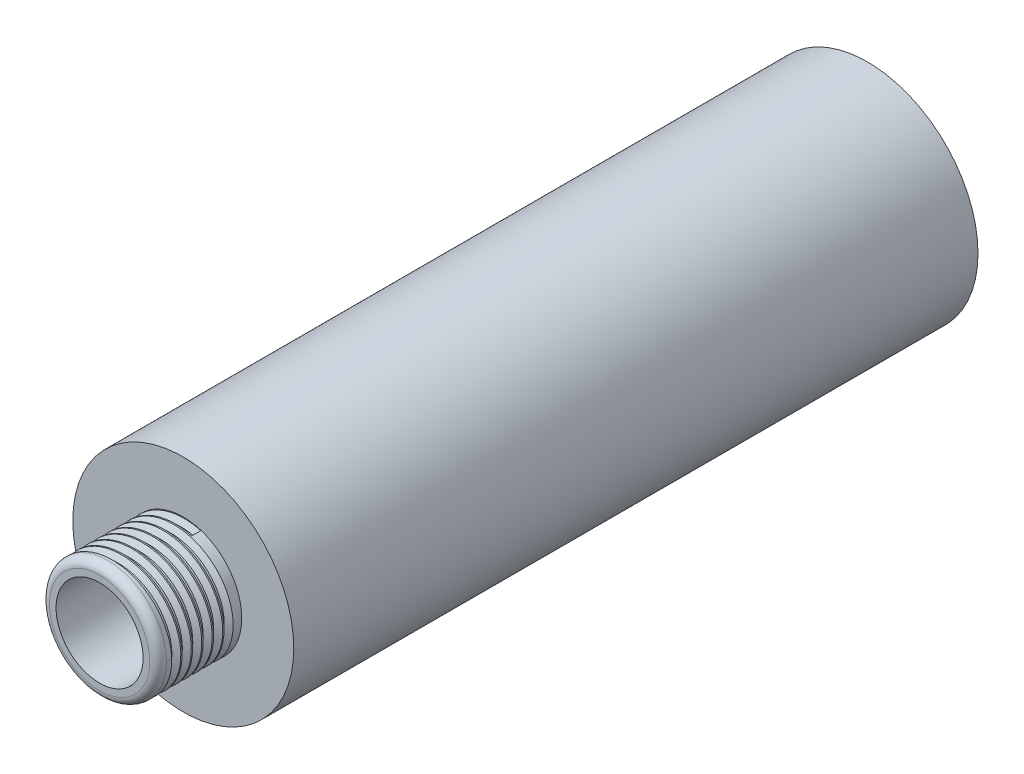
SolidWorks part; units mm, degrees
ref_plane "Front Plane" through (0, 0, 0) normal (0, 0, 1) x (1, 0, 0)
ref_plane "Top Plane" through (0, 0, 0) normal (0, 1, 0) x (1, 0, 0)
ref_plane "Right Plane" through (0, 0, 0) normal (1, 0, 0) x (0, 0, -1)
sketch "Sketch1" plane through (0, 0, 0) normal (0, 0, 1) x (1, 0, 0)
  circle A0 centre (0, 0) radius 16.764
  circle A1 centre (0, 0) radius 16.2902
  dimension "D1" = 33.528
extrude "Boss-Extrude1" add sketch "Sketch1" along normal blind 100
ref_plane "Plane1" through (0, 0, 100) normal (0, 0, 1) x (1, 0, 0)
sketch "Sketch2" plane through (0, 0, 100) normal (0, 0, 1) x (1, 0, 0)
  circle A0 centre (0, 0) radius 8.8725
  circle A1 centre (0, 0) radius 6.604
extrude "Boss-Extrude2" add sketch "Sketch2" along normal blind 15.24 and the other way blind 1.364 separate body
sketch "Sketch4" plane through (0, 0, 100) normal (0, 0, 1) x (1, 0, 0)
  circle A0 centre (0, 0) radius 8.8725
  circle A1 centre (0, 0) radius 16.764
extrude "Boss-Extrude3" add sketch "Sketch4" against normal blind 2.54 and the other way blind 2.54
sketch "Sketch5" plane through (0, 0, 0) normal (0, 0, 1) x (1, 0, 0)
  circle A0 centre (0, 0) radius 16.764
extrude "Boss-Extrude4" add sketch "Sketch5" against normal blind 1.27
fillet "Fillet4" radius 1.27 1 edges at (8.8725, 0, 115.24)
thread "Thread1" pitch 1.5875 method cut profile "Thread Profile1" start angle 0, offset 0, length 10, pitch 1.5875, diameter 17.7451
ref_plane "Plane2" through (-8.8725, 0, 113.97) normal (0, -1, 0) x (-1, 0, 0)
sketch "Thread Profile1" plane through (-8.8725, 0, 113.97) normal (0, -1, 0) x (-1, 0, 0)
  line L0 (0, 0) -> (0, 1.5875) construction
  line L11 (0, 0) -> (0, 1.3891)
  line L12 (0, 1.3891) -> (-0.8593, 0.893)
  line L13 (-0.8593, 0.893) -> (-0.8593, 0.4961)
  line L15 (-0.8593, 0.4961) -> (0, 0)
  line L17 (-0.8593, 0.6945) -> (0, 0.6945) construction
  point P2 (0, 0)
  dimension "Pitch" = 1.5875
  dimension "Profile_Angle" = 60
  dimension "Profile_Land" = 0.3969
  dimension "Profile_Height" = 0.8593
